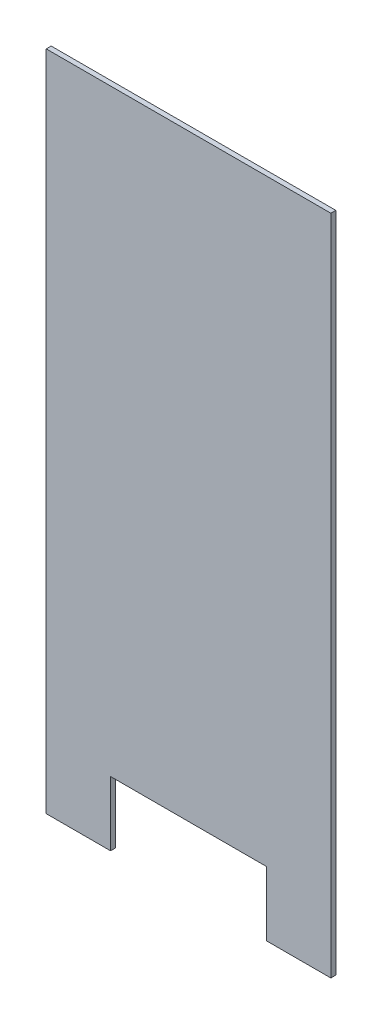
SolidWorks part; units mm, degrees
ref_plane "Front Plane" through (0, 0, 0) normal (0, 0, 1) x (1, 0, 0)
ref_plane "Top Plane" through (0, 0, 0) normal (0, 1, 0) x (1, 0, 0)
ref_plane "Right Plane" through (0, 0, 0) normal (1, 0, 0) x (0, 0, -1)
sketch "Sketch1" plane through (0, 0, 0) normal (0, 0, 1) x (1, 0, 0)
  line L0 (0, 0) -> (0, -669) construction
  line L1 (-287.5, 669) -> (287.5, 669)
  line L2 (-287.5, 669) -> (-287.5, -669)
  line L3 (-287.5, -669) -> (-157.5, -669)
  line L4 (287.5, 669) -> (287.5, -669)
  line L5 (-287.5, 669) -> (287.5, -669) construction
  line L6 (-287.5, -669) -> (287.5, 669) construction
  line L7 (157.5, -669) -> (287.5, -669)
  line L8 (-157.5, -539) -> (157.5, -539)
  line L9 (-157.5, -539) -> (-157.5, -669)
  line L11 (157.5, -539) -> (157.5, -669)
  line L12 (-157.5, -539) -> (157.5, -669) construction
  line L13 (-157.5, -669) -> (157.5, -539) construction
  point P0 (0, 0)
  point P8 (0, -604)
  dimension "D1" = 575
  dimension "D2" = 1338
  dimension "D3" = 315
  dimension "D4" = 130
extrude "Boss-Extrude1" add sketch "Sketch1" along normal blind 10
